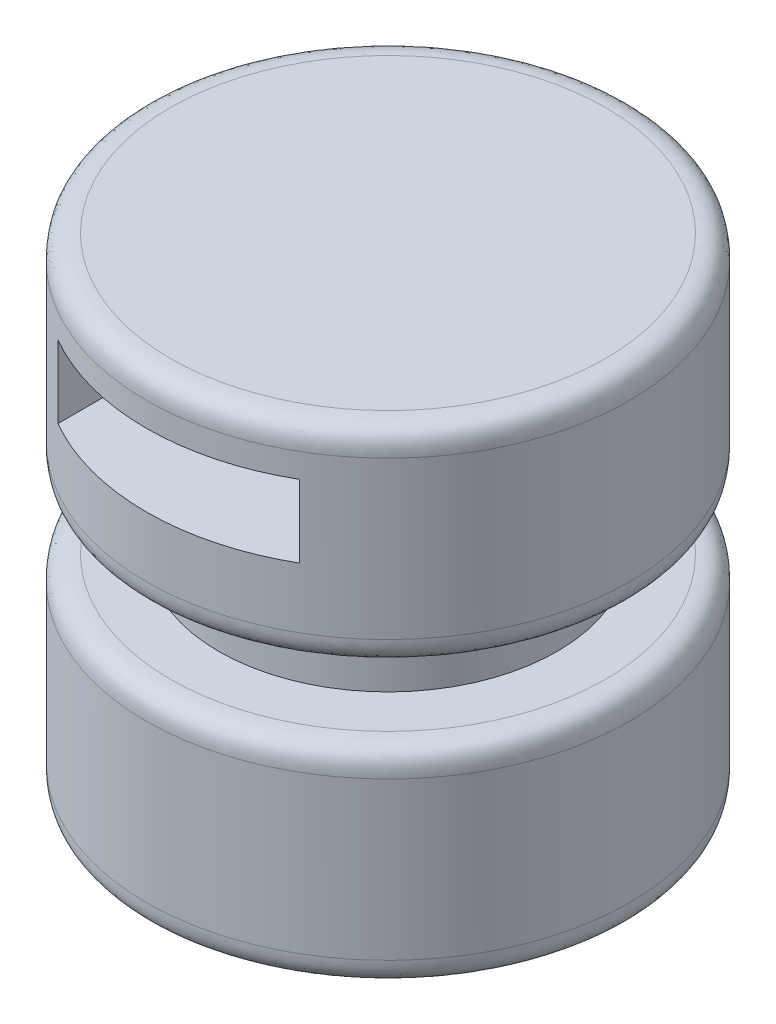
SolidWorks part; units mm, degrees
ref_plane "Front Plane" through (0, 0, 0) normal (0, 0, 1) x (1, 0, 0)
ref_plane "Top Plane" through (0, 0, 0) normal (0, 1, 0) x (1, 0, 0)
ref_plane "Right Plane" through (0, 0, 0) normal (1, 0, 0) x (0, 0, -1)
sketch "Sketch2" plane through (0, 0, 0) normal (0, 1, 0) x (1, 0, 0)
  circle A0 centre (0, 0) radius 100
  dimension "D1" = 200
extrude "Boss-Extrude1" add sketch "Sketch2" along normal blind 200
sketch "Sketch3" plane through (0, 0, 0) normal (1, 0, 0) x (0, 0, -1)
  line L0 (-100, 100) -> (100, 100) construction
  line L1 (70, 115) -> (100, 115)
  line L2 (70, 115) -> (70, 85)
  line L3 (70, 85) -> (100, 85)
  line L4 (100, 115) -> (100, 85)
  line L5 (70, 115) -> (100, 85) construction
  line L6 (70, 85) -> (100, 115) construction
  line L7 (-100, 200) -> (-100, 0) construction
  line L8 (100, 0) -> (100, 200) construction
  line L9 (0, 200) -> (0, 0) construction
  line L10 (100, 200) -> (-100, 200) construction
  point P0 (85, 100)
  point P12 (100, 100)
  dimension "D1" = 30
revolve "Cut-Revolve1" cut sketch "Sketch3" angle 360 about L9
sketch "Sketch4" plane through (0, 0, 0) normal (0, 0, 1) x (1, 0, 0)
  line L0 (0, 200) -> (0, 0) construction
  line L1 (-50, 180) -> (50, 180)
  line L2 (-50, 180) -> (-50, 150)
  line L3 (-50, 150) -> (50, 150)
  line L4 (50, 180) -> (50, 150)
  line L5 (-50, 180) -> (50, 150) construction
  line L6 (-50, 150) -> (50, 180) construction
  line L7 (100, 200) -> (-100, 200) construction
  point P0 (0, 165)
  point P10 (0, 0)
  dimension "D1" = 100
  dimension "D2" = 30
  dimension "D3" = 20
extrude "Cut-Extrude1" cut sketch "Sketch4" against normal through all both and the other way through all contours L2 L1 L4 L3
fillet "Fillet2" radius 10 4 edges at (0, 0, 100) (0, 85, 100) (0, 115, 100) (0, 200, 100) curvature continuous yes
